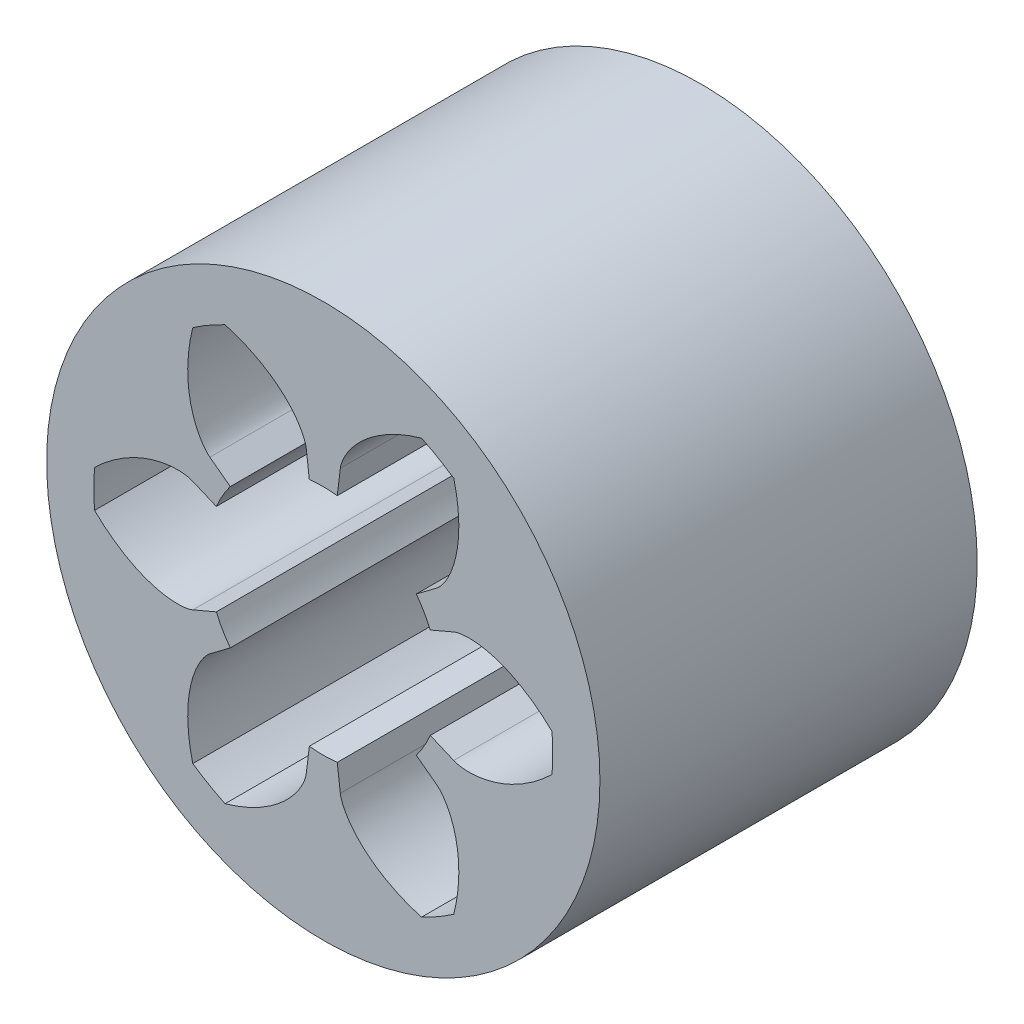
SolidWorks part; units mm, degrees
ref_plane "前视基准面" through (0, 0, 0) normal (0, 0, 1) x (1, 0, 0)
ref_plane "上视基准面" through (0, 0, 0) normal (0, 1, 0) x (1, 0, 0)
ref_plane "右视基准面" through (0, 0, 0) normal (1, 0, 0) x (0, 0, -1)
other "Configuration Table"
sketch "草图1" plane through (0, 0, 0) normal (0, 0, 1) x (1, 0, 0)
  line L0 (0, 0) -> (1.1087, 0.4592) construction
  line L1 (0, 0) -> (1.0372, 0.4425)
  line L2 (0, 0) -> (1.0372, -0.4425)
  line L3 (0, 0) -> (1.1087, -0.4592) construction
  line L4 (0, 0) -> (1.825, 0) construction
  line L5 (1.1087, 0.4592) -> (1.1087, -0.4592) construction
  circle A0 centre (0, 0) radius 0.925
  circle A1 centre (0, 0) radius 1.825
  circle A2 centre (0, 0) radius 1.1276 construction
  circle A3 centre (0, 0) radius 1.2 construction
  circle A4 centre (0, 0) radius 2.2
  spline S0 degree 4 poles (1.0372, 0.4425) (1.0451, 0.4458) (1.0679, 0.4536) (1.1133, 0.4615) (1.188, 0.4641) (1.2844, 0.4524) (1.4047, 0.4201) (1.5384, 0.3613) (1.6746, 0.2764) (1.8072, 0.1656) (1.9251, 0.0393) (2.0279, -0.0995) (2.12, -0.2556) (2.2132, -0.4598) (2.2925, -0.7157) (2.34, -1.0237) (2.3398, -1.3696) (2.2891, -1.712) (2.1939, -2.0438) (2.0552, -2.3616) (1.8823, -2.6586) (1.6708, -2.936) (1.4388, -3.184) (1.166, -3.413) (0.9461, -3.5671) (0.6842, -3.7168) (0.5292, -3.7919) (0.3505, -3.8722) (0.2497, -3.9065) (0.1672, -3.9381) (0.1423, -3.9451) (0.1243, -3.9513) knots 0 0 0 0 0 0.005604 0.015718 0.02996 0.048734 0.068727 0.096889 0.125051 0.153212 0.181374 0.209535 0.237696 0.271429 0.327752 0.384075 0.440398 0.496721 0.553044 0.609367 0.66569 0.722013 0.778336 0.834659 0.890982 0.909091 0.954545 0.977273 0.988636 1 1 1 1 1 construction
  spline S1 degree 4 poles (1.0372, 0.4425) (1.0451, 0.4458) (1.0679, 0.4536) (1.1133, 0.4615) (1.188, 0.4641) (1.2844, 0.4524) (1.4047, 0.4201) (1.5384, 0.3613) (1.6746, 0.2764) (1.8072, 0.1656) (1.9251, 0.0393) (2.0279, -0.0995) (2.12, -0.2556) (2.2132, -0.4598) (2.2925, -0.7157) (2.34, -1.0237) (2.3398, -1.3696) (2.2891, -1.712) (2.1939, -2.0438) (2.0552, -2.3616) (1.8823, -2.6586) (1.6708, -2.936) (1.4388, -3.184) (1.166, -3.413) (0.9461, -3.5671) (0.7517, -3.6782) (0.6596, -3.7265) (0.6372, -3.738) knots 0 0 0 0 0 0.005604 0.015718 0.02996 0.048734 0.068727 0.096889 0.125051 0.153212 0.181374 0.209535 0.237696 0.271429 0.327752 0.384075 0.440398 0.496721 0.553044 0.609367 0.66569 0.722013 0.778336 0.834659 0.890982 0.909091 0.909091 0.909091 0.909091 0.909091
  spline S2 degree 4 poles (1.0372, -0.4425) (1.0451, -0.4458) (1.0679, -0.4536) (1.1133, -0.4615) (1.188, -0.4641) (1.2844, -0.4524) (1.4047, -0.4201) (1.5384, -0.3613) (1.6746, -0.2764) (1.8072, -0.1656) (1.9251, -0.0393) (2.0279, 0.0995) (2.12, 0.2556) (2.2132, 0.4598) (2.2925, 0.7157) (2.34, 1.0237) (2.3398, 1.3696) (2.2891, 1.712) (2.1939, 2.0438) (2.0552, 2.3616) (1.8823, 2.6586) (1.6708, 2.936) (1.4388, 3.184) (1.166, 3.413) (0.9461, 3.5671) (0.6842, 3.7168) (0.5292, 3.7919) (0.3505, 3.8722) (0.2497, 3.9065) (0.1672, 3.9381) (0.1423, 3.9451) (0.1243, 3.9513) knots 0 0 0 0 0 0.005604 0.015718 0.02996 0.048734 0.068727 0.096889 0.125051 0.153212 0.181374 0.209535 0.237696 0.271429 0.327752 0.384075 0.440398 0.496721 0.553044 0.609367 0.66569 0.722013 0.778336 0.834659 0.890982 0.909091 0.954545 0.977273 0.988636 1 1 1 1 1 construction
  spline S3 degree 4 poles (1.0372, -0.4425) (1.0451, -0.4458) (1.0679, -0.4536) (1.1133, -0.4615) (1.188, -0.4641) (1.2844, -0.4524) (1.4047, -0.4201) (1.5384, -0.3613) (1.6746, -0.2764) (1.8072, -0.1656) (1.9251, -0.0393) (2.0279, 0.0995) (2.12, 0.2556) (2.2132, 0.4598) (2.2925, 0.7157) (2.34, 1.0237) (2.3398, 1.3696) (2.2891, 1.712) (2.1939, 2.0438) (2.0552, 2.3616) (1.8823, 2.6586) (1.6708, 2.936) (1.4388, 3.184) (1.166, 3.413) (0.9461, 3.5671) (0.7517, 3.6782) (0.6596, 3.7265) (0.6372, 3.738) knots 0 0 0 0 0 0.005604 0.015718 0.02996 0.048734 0.068727 0.096889 0.125051 0.153212 0.181374 0.209535 0.237696 0.271429 0.327752 0.384075 0.440398 0.496721 0.553044 0.609367 0.66569 0.722013 0.778336 0.834659 0.890982 0.909091 0.909091 0.909091 0.909091 0.909091
  point P16 (1.1087, 0)
  dimension "内啮合齿顶圆直径" = 1.85
  dimension "内啮合分度圆直径" = 2.4
  dimension "内啮合基圆直径" = 2.2553
  dimension "内啮合齿根圆直径" = 3.65
  dimension "外径" = 4.4
  dimension "渐开线镜像线夹角" = 22.5
extrude "凸台-拉伸1" add sketch "草图1" along normal blind 3 contours A4 | A0
extrude "切除-拉伸2" cut sketch "草图1<3>" along normal through all contours A0 S3 A1 S1 region at (1.3095, 0, 0)
sketch "草图1<3>" plane through (0, 0, 0) normal (0, 0, 1) x (1, 0, 0) same geometry as "草图1"
pattern_circular "阵列(圆周)1" count 6 over 360 about axis through (0, 0, 3) along (0, 0, 1) of "切除-拉伸2"
equation "\"m\"= 0.4'模数"
equation "\"z1\" = 6'外啮合齿轮数"
equation "\"a\"= 20度'压力角"
equation "\"z2\"= 6'内啮合齿轮数"
equation "\"hax\"= 1'齿顶高系数"
equation "\"cx\"= 0.25'顶隙系数"
equation "\"ha\"= \"hax\" * \"m\"'齿顶高"
equation "\"hf\"= ( \"hax\" + \"cx\" ) * \"m\"'齿根高"
equation "\"d1\"= \"m\" * \"z1\"'外啮合分度圆直径"
equation "\"da1\"= ( \"z1\" + 2 ) * \"m\"'外啮合齿顶圆直径"
equation "\"df1\"= \"d1\" - 2 * \"hf\"'外啮合齿根圆直径"
equation "\"db1\"= \"d1\" * cos ( \"a\" )'外啮合基圆直径"
equation "\"p\"= \"m\" * PI'齿距"
equation "\"d2\"= \"m\" * \"z2\"'内啮合分度圆直径"
equation "\"db2\"= \"d2\" * cos ( \"a\" )'内啮合基圆直径"
equation "\"da2\"= ( \"z2\" - 2 ) * \"m\"'内啮合齿顶圆直径"
equation "\"df2\"= \"d2\" + 2 * \"hf\"'内啮合齿根圆直径"
equation "\"内啮合齿顶圆直径@草图1\" = \"da2\" + 0.5 * \"hf\""
equation "\"内啮合齿根圆直径@草图1\"= \"df2\" + 0.5 * \"hf\""
equation "\"内啮合分度圆直径@草图1\"= \"d2\""
equation "\"内啮合基圆直径@草图1\"= \"db2\""
equation "\"渐开线镜像线夹角@草图1\"= 360度 / 4 / \"z2\" + 360度 / 4 / \"z2\" / 2"
equation "\"do\"= IIF ( \"edo\" >= ( \"df2\" + 1 ) , \"edo\" , ( \"df2\" + 1 ) )'外圈直径"
equation "\"h\" = 3'厚度"
equation "\"外径@草图1\"= \"do\""
equation "\"厚度@凸台-拉伸1\"= \"h\""
equation "\"内啮合齿轮数@阵列(圆周)1\"= \"z2\""
equation "\"edo\"= 3'期望的外圈直径"
